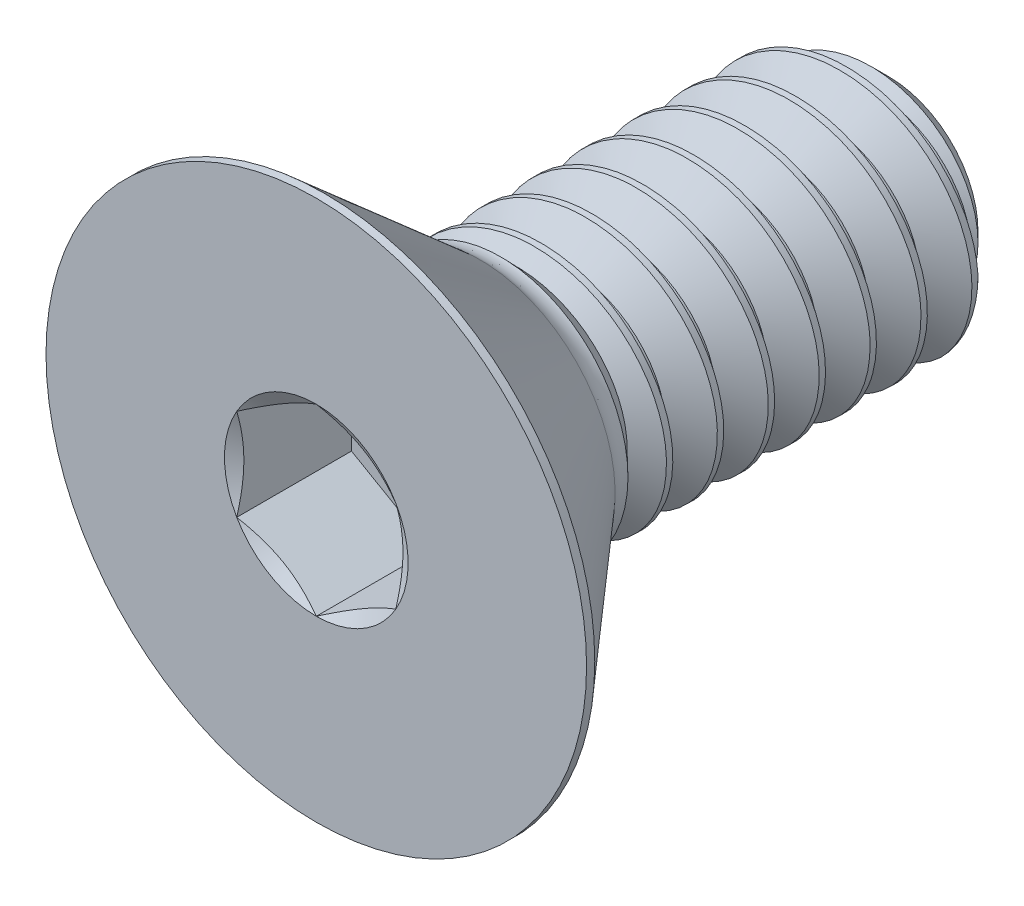
SolidWorks part; units mm, degrees
ref_plane "Front" through (0, 0, 0) normal (0, 0, 1) x (1, 0, 0)
ref_plane "Top" through (0, 0, 0) normal (0, 1, 0) x (1, 0, 0)
ref_plane "Right" through (0, 0, 0) normal (1, 0, 0) x (0, 0, -1)
sketch "Sketch1" plane through (0, 0, 0) normal (1, 0, 0) x (0, 0, -1)
  line L0 (0, 6.7437) -> (0.2045, 6.7437) construction
  line L1 (0.2045, 6.7437) -> (4.0894, 3.3666) construction
  line L2 (0, 3.175) -> (14.2875, 3.175)
  line L3 (14.2875, 3.175) -> (14.2875, 0)
  line L4 (14.2875, 0) -> (0, 0)
  line L5 (0, 0) -> (0, 6.7437) construction
  line L6 (0, 6.7437) -> (0, -6.7437) construction
  line L7 (14.2875, 3.175) -> (14.2875, -3.175) construction
  line L8 (0, -6.7437) -> (0.2045, -6.7437) construction
  line L9 (0.2045, -6.7437) -> (4.0894, -3.3666) construction
  line L11 (0, 3.175) -> (0, 0)
  line L12 (4.6018, 3.175) -> (4.6018, 0) construction
  line L13 (-11.1125, 0) -> (-11.1125, 3.175) construction
  arc A1 (4.0894, 3.3666) -> (4.6018, 3.175) centre (4.6018, 3.956) ccw construction
  dimension "D1" = 0.2045
  dimension "Head Ht" = 4.0894
  dimension "Head Dia" = 13.4874
  dimension "Dia" = 6.35
  dimension "Lg" = 14.2875
  dimension "Head Angle" = 82
  dimension "Min Thread" = 25.4
revolve "Revolve1" add sketch "Sketch1" angle 360 mid plane about L4
sketch "Sketch3" plane through (0, 0, -14.2875) normal (0, 0, -1) x (-1, 0, 0)
  circle A0 centre (0, 0) radius 3.175
curve "Helix/Spiral1" pitch 1.27 height 14.2875 radius 3.175 centre (0, 0, -14.2875) axis (0, 0, 1) start towards (0, 1, 0)
sketch "Sketch2" plane through (0, 0, 0) normal (1, 0, 0) x (0, 0, -1)
  line L0 (14.2875, 3.175) -> (15.3988, 3.175)
  line L1 (15.3988, 3.175) -> (14.9225, 2.3501)
  line L2 (14.9225, 2.3501) -> (14.7638, 2.3501)
  line L3 (14.7638, 2.3501) -> (14.2875, 3.175)
  line L4 (14.5256, 2.7626) -> (15.1606, 2.7626) construction
  dimension "D1" = 60
  dimension "D2" = 0.1588
  dimension "D3" = 0.635
ref_plane "Plane2" through (0, 0, 11.1125) normal (0, 0, 1) x (1, 0, 0)
chamfer "Chamfer1" distance 0.9525 angle 45 1 edges at (0, 3.175, -14.2875)
sweep "Cut-Sweep1" cut profiles "Sketch2" path "Helix/Spiral1" align with end faces yes
sketch "Sketch7" plane through (0, 0, 0) normal (1, 0, 0) x (0, 0, -1)
  line L0 (0, 6.7437) -> (0.2045, 6.7437) construction
  line L1 (0.2045, 6.7437) -> (4.0894, 3.3666) construction
  line L2 (0, 6.7437) -> (0.2045, 6.7437)
  line L3 (0.2045, 6.7437) -> (4.0894, 3.3666)
  line L4 (4.6018, 3.175) -> (4.6018, 0) construction
  line L5 (4.6018, 3.175) -> (4.6018, 0)
  line L7 (0, 0) -> (0, 6.7437) construction
  line L8 (0, 0) -> (0, 6.7437)
  line L9 (0, 0) -> (4.6018, 0)
  line L10 (5.7417, 0) -> (-5.7417, 0) construction
  arc A0 (4.0894, 3.3666) -> (4.6018, 3.175) centre (4.6018, 3.956) ccw construction
  arc A1 (4.0894, 3.3666) -> (4.6018, 3.175) centre (4.6018, 3.956) ccw
revolve "Revolve2" add sketch "Sketch7" angle 360 mid plane about L9
ref_plane "Plane1" through (0, 0, -4.6018) normal (0, 0, 1) x (1, 0, 0)
sketch "Sketch8" plane through (0, 0, -4.6018) normal (0, 0, 1) x (1, 0, 0)
  circle A0 centre (0, 0) radius 3.175
extrude "Boss-Extrude1" add sketch "Sketch8" against normal through all draft 46
sketch "Sketch5" plane through (0, 0, 0) normal (0, 0, 1) x (1, 0, 0)
  line L0 (0, 0) -> (-2.2914, 0) construction
  line L1 (0, 0) -> (-2.7496, 1.5875) construction
  line L2 (0, 0) -> (-2.7496, -1.5875) construction
  line L6 (0, 2.2914) -> (0, 1.8898) construction
  line L7 (0, 1.8898) -> (0, 1.4883) construction
  line L9 (0, 2.2914) -> (-1.9844, 1.1457)
  line L10 (-1.9844, 1.1457) -> (-1.9844, -1.1457)
  line L11 (-1.9844, -1.1457) -> (0, -2.2914)
  line L12 (0, -2.2914) -> (1.9844, -1.1457)
  line L13 (1.9844, -1.1457) -> (1.9844, 1.1457)
  line L14 (1.9844, 1.1457) -> (0, 2.2914)
  circle A0 centre (0, 0) radius 2.2914 construction
  circle A1 centre (0, 0) radius 1.8898 construction
  circle A2 centre (0, 0) radius 1.4883 construction
  circle A3 centre (0, 0) radius 1.9844 construction
  dimension "D3" = 2.9766
  dimension "Hex" = 3.9688
  dimension "D4" = 30
  dimension "D5" = 30
extrude "Cut-Extrude2" cut sketch "Sketch5" against normal blind 2.8626
sketch "Sketch6" plane through (0, 0, 0) normal (0, 0, 1) x (1, 0, 0)
  circle A0 centre (0, 0) radius 2.2914
extrude "Cut-Extrude3" cut sketch "Sketch6" against normal blind 2.8626 draft 60
sketch "Sketch9" [suppressed] plane through (0, 0, -3.6076) normal (0, 0, 1) x (1, 0, 0)
  circle A1 centre (0, 0) radius 2.413
  circle A2 centre (0, 0) radius 2.413
  point P0 (0, 2.413)
  dimension "D1" = 0
extrude "Boss-Extrude2" [suppressed] add sketch "Sketch9" against normal up to surface (15.4424 mm away) up to plane "Plane2"
sketch "Sketch10" plane through (0, 0, 0) normal (1, 0, 0) x (0, 0, -1)
  line L0 (14.2875, 3.175) -> (14.2875, -3.175) construction
  point P0 (12.3825, -3.175)
  dimension "D1" = 1.905
equation "\"D3@Helix/Spiral1\" = \"Lg@Sketch1\""
equation "\"D2@Sketch2\" = \"D4@Helix/Spiral1\" * .125"
equation "\"D3@Sketch2\" = \"D4@Helix/Spiral1\" * .5"
equation "\"D1@Chamfer1\" = \"D4@Helix/Spiral1\" * .75"
equation "\"D1@Cut-Extrude2\" = \"Head Ht@Sketch1\" * .7"
equation "\"D1@Sketch1\" = \"Head Ht@Sketch1\" * .05"
equation "\"D1@Sketch10\" = \"D4@Helix/Spiral1\" * 1.5"
equation "\"D1@Cut-Extrude3\" = \"D1@Cut-Extrude2\""
equation "\"D3@Sketch5\" = \"Hex@Sketch5\" * .75"
